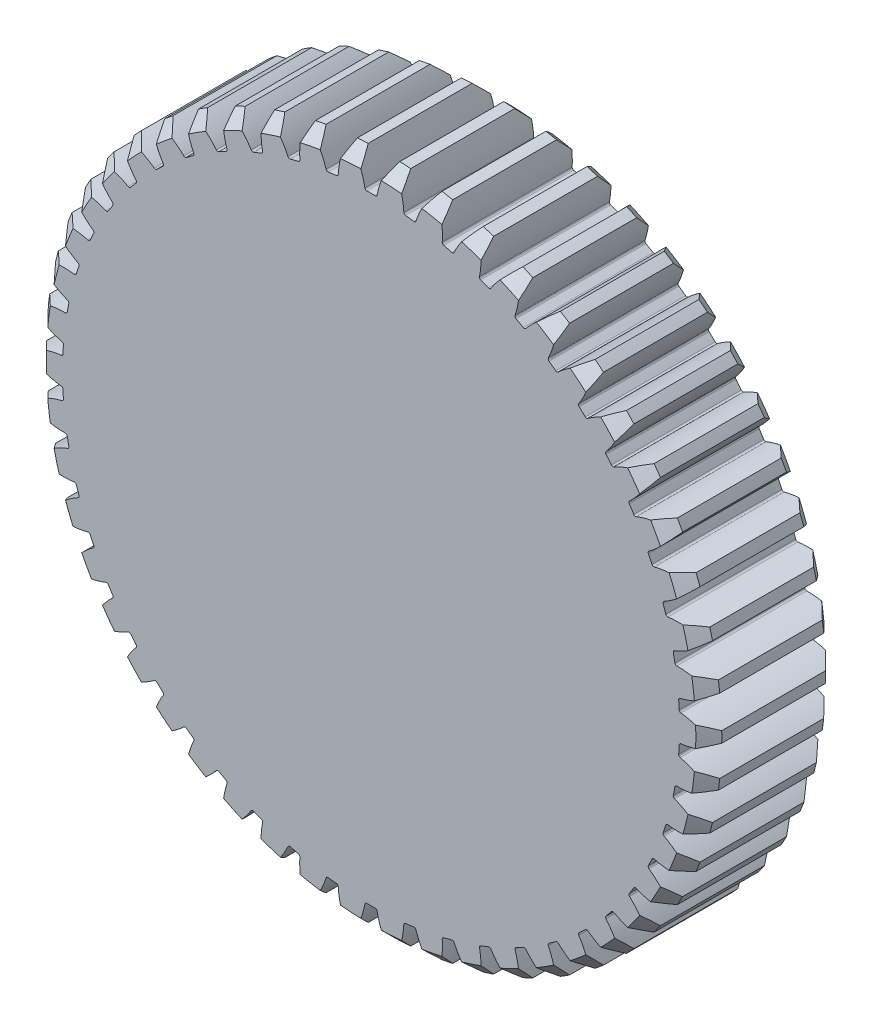
SolidWorks part; units mm, degrees
ref_plane "前视基准面" through (0, 0, 0) normal (0, 0, 1) x (1, 0, 0)
ref_plane "上视基准面" through (0, 0, 0) normal (0, 1, 0) x (1, 0, 0)
ref_plane "右视基准面" through (0, 0, 0) normal (1, 0, 0) x (0, 0, -1)
sketch "直齿轮" plane through (0, 0, 0) normal (0, 0, 1) x (1, 0, 0)
  line L0 (0, 52) -> (0, -52) construction
  line L1 (0, 0) -> (-0.8583, 46.9768)
  line L2 (0, 0) -> (0.8583, 46.9768)
  circle A0 centre (0, 0) radius 52
  arc A1 (1.5705, 49.9753) -> (-1.5705, 49.9753) centre (0, 0) ccw
  circle A2 centre (0, 0) radius 47.5
  circle A3 centre (0, 0) radius 46.9846
  spline S0 degree 4 poles (-0.8583, 46.9768) (-0.8591, 47.0215) (-0.8627, 47.1107) (-0.8774, 47.2888) (-0.9114, 47.5548) (-0.9634, 47.8631) (-1.0512, 48.2834) (-1.1738, 48.7694) (-1.3375, 49.3188) (-1.5479, 49.9285) (-1.8873, 50.8029) (-2.3957, 51.9244) (-3.1831, 53.3966) (-4.321, 55.1701) (-6.085, 57.5082) (-8.9914, 60.6451) (-13.2058, 64.156) (-18.9041, 67.6529) (-25.5044, 70.5369) (-32.4069, 72.5821) (-39.4937, 73.8344) (-47.0256, 74.3638) (-56.3705, 74.0437) (-67.3907, 72.2355) (-79.7562, 68.2868) (-91.0369, 62.6378) (-100.0387, 56.6817) (-108.4482, 49.9339) (-114.9346, 43.7045) (-120.8653, 36.9461) (-126.217, 29.7306) (-130.1437, 23.7114) (-133.7101, 17.4723) (-136.9122, 11.0388) (-139.3931, 5.261) (-141.2893, 0.2173) (-142.7161, -4.0395) (-143.7655, -7.4745) (-144.7229, -10.9362) (-145.5886, -14.422) (-146.3627, -17.9291) (-147.0456, -21.4554) (-147.6376, -24.9975) (-148.0764, -28.11) (-148.3962, -30.7836) (-148.6254, -33.018) (-148.7863, -34.8035) (-148.925, -36.5993) (-149.0413, -38.3814) (-149.1273, -40.0312) (-149.1885, -41.4781) (-149.2314, -42.8373) (-149.2589, -43.9054) (-149.2809, -45.3186) (-149.2888, -46.3272) (-149.2898, -47.9771) (-149.2726, -49.254) (-149.2437, -50.8034) (-149.1994, -52.196) (-149.1273, -54.0393) (-149.0315, -55.8247) (-148.9128, -57.6471) (-148.7709, -59.4448) (-148.6437, -60.8927) (-148.4674, -62.6927) (-148.2684, -64.4954) (-148.0468, -66.2915) (-147.8515, -67.7286) (-147.7493, -68.4453) (-147.6971, -68.8041) knots 0 0 0 0 0 0.000701 0.001401 0.002802 0.004203 0.005604 0.008133 0.010661 0.01319 0.015718 0.022839 0.02996 0.039347 0.048734 0.068727 0.096889 0.125051 0.153212 0.181374 0.209535 0.237696 0.271429 0.327752 0.384075 0.440398 0.46856 0.496721 0.553044 0.581206 0.609367 0.637529 0.66569 0.693852 0.722013 0.736094 0.750174 0.764255 0.778336 0.792417 0.806497 0.820578 0.834659 0.84874 0.85578 0.86282 0.869861 0.876901 0.883942 0.890982 0.895509 0.900036 0.904564 0.909091 0.914773 0.920455 0.926136 0.931818 0.9375 0.943182 0.954545 0.960227 0.965909 0.971591 0.977273 0.988636 0.994318 1 1 1 1 1 construction
  spline S1 degree 4 poles (-0.8583, 46.9768) (-0.8591, 47.0215) (-0.8627, 47.1107) (-0.8774, 47.2888) (-0.9114, 47.5548) (-0.9634, 47.8631) (-1.0512, 48.2834) (-1.1738, 48.7694) (-1.3375, 49.3188) (-1.5479, 49.9285) (-1.8873, 50.8029) (-2.3957, 51.9244) (-3.1831, 53.3966) (-4.321, 55.1701) (-6.085, 57.5082) (-8.9914, 60.6451) (-13.2058, 64.156) (-18.9041, 67.6529) (-25.5044, 70.5369) (-32.4069, 72.5821) (-39.4937, 73.8344) (-47.0256, 74.3638) (-56.3705, 74.0437) (-67.3907, 72.2355) (-79.7562, 68.2868) (-91.0369, 62.6378) (-100.0387, 56.6817) (-108.4482, 49.9339) (-114.9346, 43.7045) (-120.8653, 36.9461) (-126.217, 29.7306) (-130.1437, 23.7114) (-133.7101, 17.4723) (-136.9122, 11.0388) (-139.3931, 5.261) (-141.2893, 0.2173) (-142.7161, -4.0395) (-143.7655, -7.4745) (-144.7229, -10.9362) (-145.5886, -14.422) (-146.3627, -17.9291) (-147.0456, -21.4554) (-147.6376, -24.9975) (-148.0764, -28.11) (-148.3962, -30.7836) (-148.6254, -33.018) (-148.7863, -34.8035) (-148.925, -36.5993) (-149.0413, -38.3814) (-149.1273, -40.0312) (-149.1885, -41.4781) (-149.2314, -42.8373) (-149.2589, -43.9054) (-149.2744, -44.9018) (-149.2805, -45.4327) (-149.2828, -45.6951) knots 0 0 0 0 0 0.000701 0.001401 0.002802 0.004203 0.005604 0.008133 0.010661 0.01319 0.015718 0.022839 0.02996 0.039347 0.048734 0.068727 0.096889 0.125051 0.153212 0.181374 0.209535 0.237696 0.271429 0.327752 0.384075 0.440398 0.46856 0.496721 0.553044 0.581206 0.609367 0.637529 0.66569 0.693852 0.722013 0.736094 0.750174 0.764255 0.778336 0.792417 0.806497 0.820578 0.834659 0.84874 0.85578 0.86282 0.869861 0.876901 0.883942 0.890982 0.895509 0.900036 0.904564 0.909091 0.909091 0.909091 0.909091 0.909091
  spline S2 degree 4 poles (0.8583, 46.9768) (0.8591, 47.0215) (0.8627, 47.1107) (0.8774, 47.2888) (0.9114, 47.5548) (0.9634, 47.8631) (1.0512, 48.2834) (1.1738, 48.7694) (1.3375, 49.3188) (1.5479, 49.9285) (1.8873, 50.8029) (2.3957, 51.9244) (3.1831, 53.3966) (4.321, 55.1701) (6.085, 57.5082) (8.9914, 60.6451) (13.2058, 64.156) (18.9041, 67.6529) (25.5044, 70.5369) (32.4069, 72.5821) (39.4937, 73.8344) (47.0256, 74.3638) (56.3705, 74.0437) (67.3907, 72.2355) (79.7562, 68.2868) (91.0369, 62.6378) (100.0387, 56.6817) (108.4482, 49.9339) (114.9346, 43.7045) (120.8653, 36.9461) (126.217, 29.7306) (130.1437, 23.7114) (133.7101, 17.4723) (136.9122, 11.0388) (139.3931, 5.261) (141.2893, 0.2173) (142.7161, -4.0395) (143.7655, -7.4745) (144.7229, -10.9362) (145.5886, -14.422) (146.3627, -17.9291) (147.0456, -21.4554) (147.6376, -24.9975) (148.0764, -28.11) (148.3962, -30.7836) (148.6254, -33.018) (148.7863, -34.8035) (148.925, -36.5993) (149.0413, -38.3814) (149.1273, -40.0312) (149.1885, -41.4781) (149.2314, -42.8373) (149.2589, -43.9054) (149.2809, -45.3186) (149.2888, -46.3272) (149.2898, -47.9771) (149.2726, -49.254) (149.2437, -50.8034) (149.1994, -52.196) (149.1273, -54.0393) (149.0315, -55.8247) (148.9128, -57.6471) (148.7709, -59.4448) (148.6437, -60.8927) (148.4674, -62.6927) (148.2684, -64.4954) (148.0468, -66.2915) (147.8515, -67.7286) (147.7493, -68.4453) (147.6971, -68.8041) knots 0 0 0 0 0 0.000701 0.001401 0.002802 0.004203 0.005604 0.008133 0.010661 0.01319 0.015718 0.022839 0.02996 0.039347 0.048734 0.068727 0.096889 0.125051 0.153212 0.181374 0.209535 0.237696 0.271429 0.327752 0.384075 0.440398 0.46856 0.496721 0.553044 0.581206 0.609367 0.637529 0.66569 0.693852 0.722013 0.736094 0.750174 0.764255 0.778336 0.792417 0.806497 0.820578 0.834659 0.84874 0.85578 0.86282 0.869861 0.876901 0.883942 0.890982 0.895509 0.900036 0.904564 0.909091 0.914773 0.920455 0.926136 0.931818 0.9375 0.943182 0.954545 0.960227 0.965909 0.971591 0.977273 0.988636 0.994318 1 1 1 1 1 construction
  spline S3 degree 4 poles (0.8583, 46.9768) (0.8591, 47.0215) (0.8627, 47.1107) (0.8774, 47.2888) (0.9114, 47.5548) (0.9634, 47.8631) (1.0512, 48.2834) (1.1738, 48.7694) (1.3375, 49.3188) (1.5479, 49.9285) (1.8873, 50.8029) (2.3957, 51.9244) (3.1831, 53.3966) (4.321, 55.1701) (6.085, 57.5082) (8.9914, 60.6451) (13.2058, 64.156) (18.9041, 67.6529) (25.5044, 70.5369) (32.4069, 72.5821) (39.4937, 73.8344) (47.0256, 74.3638) (56.3705, 74.0437) (67.3907, 72.2355) (79.7562, 68.2868) (91.0369, 62.6378) (100.0387, 56.6817) (108.4482, 49.9339) (114.9346, 43.7045) (120.8653, 36.9461) (126.217, 29.7306) (130.1437, 23.7114) (133.7101, 17.4723) (136.9122, 11.0388) (139.3931, 5.261) (141.2893, 0.2173) (142.7161, -4.0395) (143.7655, -7.4745) (144.7229, -10.9362) (145.5886, -14.422) (146.3627, -17.9291) (147.0456, -21.4554) (147.6376, -24.9975) (148.0764, -28.11) (148.3962, -30.7836) (148.6254, -33.018) (148.7863, -34.8035) (148.925, -36.5993) (149.0413, -38.3814) (149.1273, -40.0312) (149.1885, -41.4781) (149.2314, -42.8373) (149.2589, -43.9054) (149.2744, -44.9018) (149.2805, -45.4327) (149.2828, -45.6951) knots 0 0 0 0 0 0.000701 0.001401 0.002802 0.004203 0.005604 0.008133 0.010661 0.01319 0.015718 0.022839 0.02996 0.039347 0.048734 0.068727 0.096889 0.125051 0.153212 0.181374 0.209535 0.237696 0.271429 0.327752 0.384075 0.440398 0.46856 0.496721 0.553044 0.581206 0.609367 0.637529 0.66569 0.693852 0.722013 0.736094 0.750174 0.764255 0.778336 0.792417 0.806497 0.820578 0.834659 0.84874 0.85578 0.86282 0.869861 0.876901 0.883942 0.890982 0.895509 0.900036 0.904564 0.909091 0.909091 0.909091 0.909091 0.909091
  dimension "齿顶圆" = 104
  dimension "分度圆" = 100
  dimension "齿根圆" = 95
  dimension "基圆直径" = 93.9693
  dimension "D1" = 3.1416
extrude "齿轮毛坯" add sketch "直齿轮" along normal mid plane 20 contours A0
chamfer "轮齿倒角" distance 2 angle 45 2 edges at (52, 0, -10) (52, 0, 10)
sketch "草图2" plane through (0, 0, 0) normal (0, 0, 1) x (1, 0, 0)
  line L0 (0, 0) -> (-0.8583, 46.9768) construction
  line L1 (0, 0) -> (0.8583, 46.9768) construction
  line L2 (0, 0) -> (-0.8583, 46.9768)
  line L3 (0, 0) -> (0.8583, 46.9768)
  circle A0 centre (0, 0) radius 52 construction
  circle A1 centre (0, 0) radius 52
  circle A2 centre (0, 0) radius 47.5 construction
  circle A3 centre (0, 0) radius 47.5
  spline S0 degree 4 poles (998.3211, 29.695) (-27.5289, 40.9407) (-1.5082, 43.0307) (-0.6251, 45.3103) (-0.9114, 47.5548) (-0.9634, 47.8631) (-1.0512, 48.2834) (-1.1738, 48.7694) (-1.3375, 49.3188) (-1.5479, 49.9285) (-1.8873, 50.8029) (-2.3957, 51.9244) (-3.1831, 53.3966) (-4.321, 55.1701) (-6.085, 57.5082) (-8.9914, 60.6451) (-13.2058, 64.156) (-18.9041, 67.6529) (-25.5044, 70.5369) (-32.4069, 72.5821) (-39.4937, 73.8344) (-47.0256, 74.3638) (-56.3705, 74.0437) (-67.3907, 72.2355) (-79.7562, 68.2868) (-91.0369, 62.6378) (-100.0387, 56.6817) (-108.4482, 49.9339) (-114.9346, 43.7045) (-120.8653, 36.9461) (-126.217, 29.7306) (-130.1437, 23.7114) (-133.7101, 17.4723) (-136.9122, 11.0388) (-139.3931, 5.261) (-141.2893, 0.2173) (-142.7161, -4.0395) (-143.7655, -7.4745) (-144.7229, -10.9362) (-145.5886, -14.422) (-146.3627, -17.9291) (-147.0456, -21.4554) (-147.6376, -24.9975) (-148.0764, -28.11) (-148.3962, -30.7836) (-148.6254, -33.018) (-148.7863, -34.8035) (-148.925, -36.5993) (-149.0413, -38.3814) (-149.1273, -40.0312) (-149.1885, -41.4781) (-149.2314, -42.8373) (-149.3341, -46.8298) (-149.3199, -54.7807) (-148.6897, -6.0085) (-157.5103, -1045.5619) knots -0.031272 -0.031272 -0.031272 -0.031272 -0.031272 0.000701 0.001401 0.002802 0.004203 0.005604 0.008133 0.010661 0.01319 0.015718 0.022839 0.02996 0.039347 0.048734 0.068727 0.096889 0.125051 0.153212 0.181374 0.209535 0.237696 0.271429 0.327752 0.384075 0.440398 0.46856 0.496721 0.553044 0.581206 0.609367 0.637529 0.66569 0.693852 0.722013 0.736094 0.750174 0.764255 0.778336 0.792417 0.806497 0.820578 0.834659 0.84874 0.85578 0.86282 0.869861 0.876901 0.883942 0.890982 0.895509 0.900036 0.904564 0.958675 0.958675 0.958675 0.958675 0.958675 only from (-0.8583, 46.9768) to (-149.2828, -45.6951) construction
  spline S1 degree 4 poles (-0.8583, 46.9768) (-0.8591, 47.0215) (-0.8627, 47.1107) (-0.8774, 47.2888) (-0.9114, 47.5548) (-0.9634, 47.8631) (-1.0512, 48.2834) (-1.1738, 48.7694) (-1.3375, 49.3188) (-1.5479, 49.9285) (-1.8873, 50.8029) (-2.3957, 51.9244) (-3.1831, 53.3966) (-4.321, 55.1701) (-6.085, 57.5082) (-8.9914, 60.6451) (-13.2058, 64.156) (-18.9041, 67.6529) (-25.5044, 70.5369) (-32.4069, 72.5821) (-39.4937, 73.8344) (-47.0256, 74.3638) (-56.3705, 74.0437) (-67.3907, 72.2355) (-79.7562, 68.2868) (-91.0369, 62.6378) (-100.0387, 56.6817) (-108.4482, 49.9339) (-114.9346, 43.7045) (-120.8653, 36.9461) (-126.217, 29.7306) (-130.1437, 23.7114) (-133.7101, 17.4723) (-136.9122, 11.0388) (-139.3931, 5.261) (-141.2893, 0.2173) (-142.7161, -4.0395) (-143.7655, -7.4745) (-144.7229, -10.9362) (-145.5886, -14.422) (-146.3627, -17.9291) (-147.0456, -21.4554) (-147.6376, -24.9975) (-148.0764, -28.11) (-148.3962, -30.7836) (-148.6254, -33.018) (-148.7863, -34.8035) (-148.925, -36.5993) (-149.0413, -38.3814) (-149.1273, -40.0312) (-149.1885, -41.4781) (-149.2314, -42.8373) (-149.2589, -43.9054) (-149.2744, -44.9018) (-149.2805, -45.4327) (-149.2828, -45.6951) knots 0 0 0 0 0 0.000701 0.001401 0.002802 0.004203 0.005604 0.008133 0.010661 0.01319 0.015718 0.022839 0.02996 0.039347 0.048734 0.068727 0.096889 0.125051 0.153212 0.181374 0.209535 0.237696 0.271429 0.327752 0.384075 0.440398 0.46856 0.496721 0.553044 0.581206 0.609367 0.637529 0.66569 0.693852 0.722013 0.736094 0.750174 0.764255 0.778336 0.792417 0.806497 0.820578 0.834659 0.84874 0.85578 0.86282 0.869861 0.876901 0.883942 0.890982 0.895509 0.900036 0.904564 0.909091 0.909091 0.909091 0.909091 0.909091
  spline S2 degree 4 poles (-998.3211, 29.695) (27.5289, 40.9407) (1.5082, 43.0307) (0.6251, 45.3103) (0.9114, 47.5548) (0.9634, 47.8631) (1.0512, 48.2834) (1.1738, 48.7694) (1.3375, 49.3188) (1.5479, 49.9285) (1.8873, 50.8029) (2.3957, 51.9244) (3.1831, 53.3966) (4.321, 55.1701) (6.085, 57.5082) (8.9914, 60.6451) (13.2058, 64.156) (18.9041, 67.6529) (25.5044, 70.5369) (32.4069, 72.5821) (39.4937, 73.8344) (47.0256, 74.3638) (56.3705, 74.0437) (67.3907, 72.2355) (79.7562, 68.2868) (91.0369, 62.6378) (100.0387, 56.6817) (108.4482, 49.9339) (114.9346, 43.7045) (120.8653, 36.9461) (126.217, 29.7306) (130.1437, 23.7114) (133.7101, 17.4723) (136.9122, 11.0388) (139.3931, 5.261) (141.2893, 0.2173) (142.7161, -4.0395) (143.7655, -7.4745) (144.7229, -10.9362) (145.5886, -14.422) (146.3627, -17.9291) (147.0456, -21.4554) (147.6376, -24.9975) (148.0764, -28.11) (148.3962, -30.7836) (148.6254, -33.018) (148.7863, -34.8035) (148.925, -36.5993) (149.0413, -38.3814) (149.1273, -40.0312) (149.1885, -41.4781) (149.2314, -42.8373) (149.3341, -46.8298) (149.3199, -54.7807) (148.6897, -6.0085) (157.5103, -1045.5619) knots -0.031272 -0.031272 -0.031272 -0.031272 -0.031272 0.000701 0.001401 0.002802 0.004203 0.005604 0.008133 0.010661 0.01319 0.015718 0.022839 0.02996 0.039347 0.048734 0.068727 0.096889 0.125051 0.153212 0.181374 0.209535 0.237696 0.271429 0.327752 0.384075 0.440398 0.46856 0.496721 0.553044 0.581206 0.609367 0.637529 0.66569 0.693852 0.722013 0.736094 0.750174 0.764255 0.778336 0.792417 0.806497 0.820578 0.834659 0.84874 0.85578 0.86282 0.869861 0.876901 0.883942 0.890982 0.895509 0.900036 0.904564 0.958675 0.958675 0.958675 0.958675 0.958675 only from (0.8583, 46.9768) to (149.2828, -45.6951) construction
  spline S3 degree 4 poles (0.8583, 46.9768) (0.8591, 47.0215) (0.8627, 47.1107) (0.8774, 47.2888) (0.9114, 47.5548) (0.9634, 47.8631) (1.0512, 48.2834) (1.1738, 48.7694) (1.3375, 49.3188) (1.5479, 49.9285) (1.8873, 50.8029) (2.3957, 51.9244) (3.1831, 53.3966) (4.321, 55.1701) (6.085, 57.5082) (8.9914, 60.6451) (13.2058, 64.156) (18.9041, 67.6529) (25.5044, 70.5369) (32.4069, 72.5821) (39.4937, 73.8344) (47.0256, 74.3638) (56.3705, 74.0437) (67.3907, 72.2355) (79.7562, 68.2868) (91.0369, 62.6378) (100.0387, 56.6817) (108.4482, 49.9339) (114.9346, 43.7045) (120.8653, 36.9461) (126.217, 29.7306) (130.1437, 23.7114) (133.7101, 17.4723) (136.9122, 11.0388) (139.3931, 5.261) (141.2893, 0.2173) (142.7161, -4.0395) (143.7655, -7.4745) (144.7229, -10.9362) (145.5886, -14.422) (146.3627, -17.9291) (147.0456, -21.4554) (147.6376, -24.9975) (148.0764, -28.11) (148.3962, -30.7836) (148.6254, -33.018) (148.7863, -34.8035) (148.925, -36.5993) (149.0413, -38.3814) (149.1273, -40.0312) (149.1885, -41.4781) (149.2314, -42.8373) (149.2589, -43.9054) (149.2744, -44.9018) (149.2805, -45.4327) (149.2828, -45.6951) knots 0 0 0 0 0 0.000701 0.001401 0.002802 0.004203 0.005604 0.008133 0.010661 0.01319 0.015718 0.022839 0.02996 0.039347 0.048734 0.068727 0.096889 0.125051 0.153212 0.181374 0.209535 0.237696 0.271429 0.327752 0.384075 0.440398 0.46856 0.496721 0.553044 0.581206 0.609367 0.637529 0.66569 0.693852 0.722013 0.736094 0.750174 0.764255 0.778336 0.792417 0.806497 0.820578 0.834659 0.84874 0.85578 0.86282 0.869861 0.876901 0.883942 0.890982 0.895509 0.900036 0.904564 0.909091 0.909091 0.909091 0.909091 0.909091
extrude "插齿" cut sketch "草图2" against normal mid plane 20 contours A3 S3 A1 S1 region at (0, 50.1155, 0)
fillet "圆角1" [suppressed] radius 0.3
pattern_circular "圆周阵列1" [suppressed] count 50 over 360 of bodies 102
fillet "圆角2" radius 0.3 2 edges at (0.9048, 47.4914, 0) (-0.9048, 47.4914, 0)
pattern_circular "圆周阵列2" count 50 over 360 about axis through (0, 0, 10) along (0, 0, -1) of "插齿", "圆角2"
pattern_circular "圆周阵列3" [suppressed] count 50 over 360 of bodies 102
sketch "分度圆" plane through (0, 0, 0) normal (0, 0, 1) x (1, 0, 0)
  circle A0 centre (0, 0) radius 50 construction
equation "\"m\"= 2'模数"
equation "\"z\"= 50'齿数"
equation "\"a\"= 20'压力角（常见为20°）"
equation "\"B\"= 20'齿宽"
equation "\"C1\"= 2'轮齿倒角（若设为0，则无倒角）"
equation "\"R\"= 0.3'齿根圆角（若设为0，则无圆角）"
equation "\"x\"= 0'变位系数"
equation "\"ha\"= 1'齿顶高系数"
equation "\"c\"= 0.25'顶隙系数"
equation "\"分度圆@直齿轮\"=\"m\" * \"z\""
equation "\"齿顶圆@直齿轮\" = \"m\" * ( \"z\" + 2 * ( \"ha\" + \"x\" ) )"
equation "\"齿根圆@直齿轮\" = \"m\" * ( \"z\" - 2 * ( \"ha\" - \"x\" + \"c\" ) )"
equation "\"基圆直径@直齿轮\"= \"m\" * \"z\" * cos ( \"a\" )"
equation "\"D1@直齿轮\"= \"m\" * ( pi / 2 ) - 2 * \"m\" * tan ( \"a\" ) * \"x\"'作者：机械菌-"
equation "\"圆周阵列3\"= IIF ( \"R\">0 , \"suppressed\" , \"unsuppressed\" )"
equation "\"圆角1\"=IIF ( \"R\">0 ,IIF ( \"m\" * ( \"z\" - 2 * ( \"ha\" - \"x\" + \"c\" ) ) < \"m\" * \"z\" * cos ( \"a\" ) , \"unsuppressed\" , \"suppressed\" ) , \"suppressed\" )"
equation "\"圆周阵列1\"=IIF ( \"R\">0 , IIF ( \"m\" * ( \"z\" - 2 * ( \"ha\" - \"x\" + \"c\" ) ) < \"m\" * \"z\" * cos ( \"a\" ) , \"unsuppressed\" , \"suppressed\" ), \"suppressed\" )"
equation "\"圆角2\"=IIF ( \"R\">0 ,IIF ( \"m\" * ( \"z\" - 2 * ( \"ha\" - \"x\" + \"c\" ) ) > \"m\" * \"z\" * cos ( \"a\" ) , \"unsuppressed\" , \"suppressed\" ) , \"suppressed\" )"
equation "\"圆周阵列2\"=IIF ( \"R\">0 , IIF ( \"m\" * ( \"z\" - 2 * ( \"ha\" - \"x\" + \"c\" ) ) > \"m\" * \"z\" * cos ( \"a\" ) , \"unsuppressed\" , \"suppressed\" ), \"suppressed\" )"
equation "\"轮齿倒角\"= IIF ( \"C1\" > 0 , \"unsuppressed\" , \"suppressed\" )"
